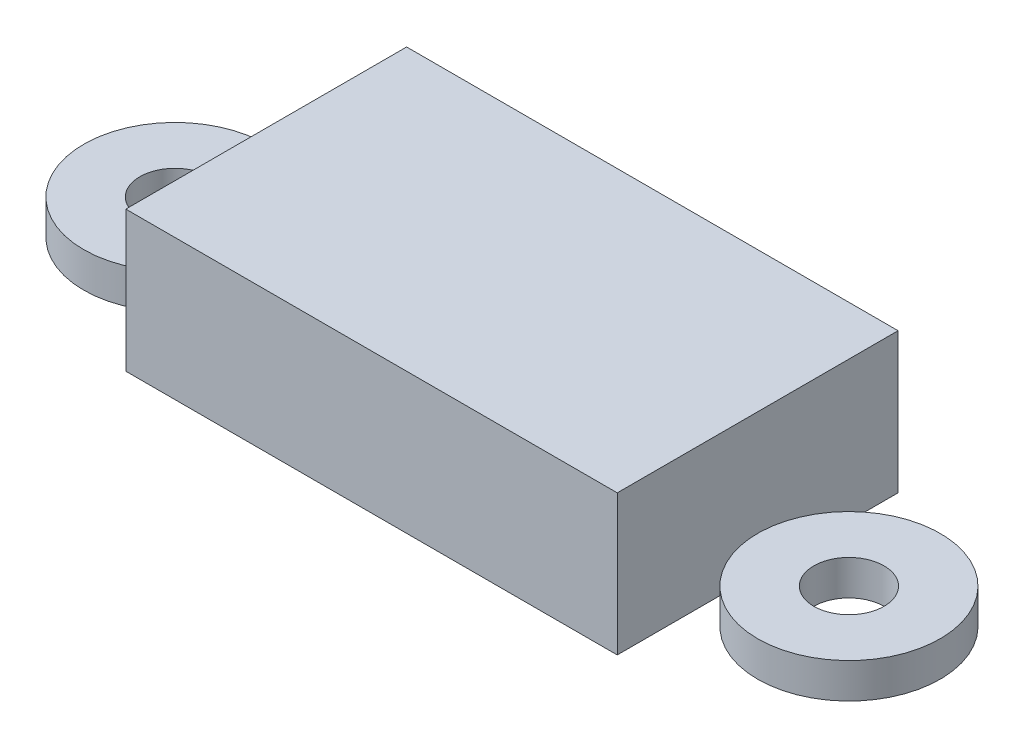
SolidWorks part; units mm, degrees
ref_plane "前视基准面" through (0, 0, 0) normal (0, 0, 1) x (1, 0, 0)
ref_plane "上视基准面" through (0, 0, 0) normal (0, 1, 0) x (1, 0, 0)
ref_plane "右视基准面" through (0, 0, 0) normal (1, 0, 0) x (0, 0, -1)
sketch "草图1" plane through (0, 0, 0) normal (0, 1, 0) x (1, 0, 0)
  line L1 (35, -20) -> (-35, -20)
  line L2 (35, -20) -> (35, 20)
  line L3 (35, 20) -> (-35, 20)
  line L4 (-35, -20) -> (-35, 20)
  line L7 (-35, 0) -> (-48, 0) construction
  line L8 (35, 0) -> (48, 0) construction
  circle A0 centre (-48, 0) radius 13
  circle A1 centre (48, 0) radius 13
  circle A2 centre (-48, 0) radius 5
  circle A3 centre (48, 0) radius 5
  point P0 (0, 0)
extrude "凸台-拉伸1" add sketch "草图1" along normal blind 20 contours L4 L1 L2 L3 region at (0, 0, 0)
sketch "草图3" plane through (0, 0, -20) normal (0, 0, -1) x (-1, 0, 0)
  line L1 (-33.1028, 1.9832) -> (33.1028, 1.9832)
  line L2 (-33.1028, 1.9832) -> (-33.1028, 17.9216)
  line L3 (-33.1028, 17.9216) -> (33.1028, 17.9216)
  line L4 (33.1028, 1.9832) -> (33.1028, 17.9216)
  point P0 (0, 9.9524)
extrude "切除-拉伸2" cut sketch "草图3" against normal blind 30
extrude "凸台-拉伸5" add sketch "草图1<8>" along normal blind 5 separate body contours A1 | A3
sketch "草图1<8>" plane through (0, 0, 0) normal (0, 1, 0) x (1, 0, 0) same geometry as "草图1"
extrude "凸台-拉伸6" add sketch "草图1<9>" along normal blind 5 separate body contours A0 | A2
sketch "草图1<9>" plane through (0, 0, 0) normal (0, 1, 0) x (1, 0, 0) same geometry as "草图1"
